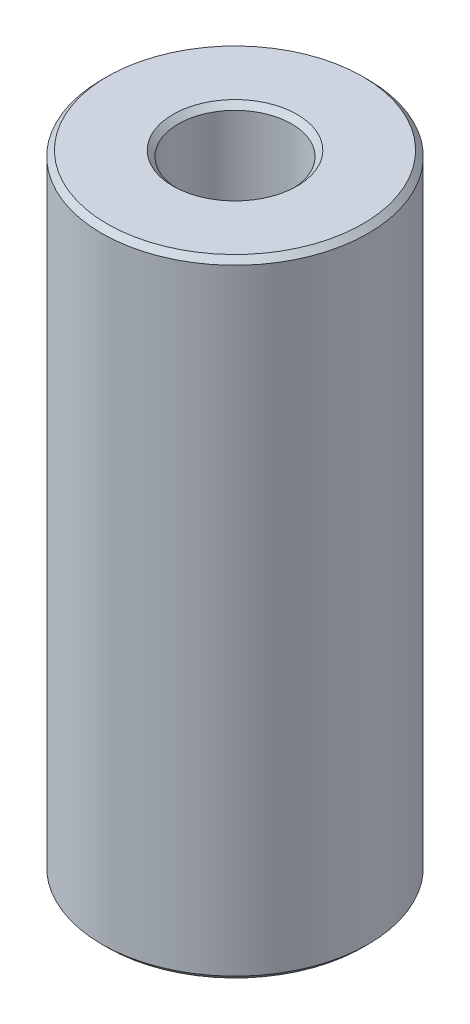
SolidWorks part; units mm, degrees
ref_plane "Front Plane" through (0, 0, 0) normal (0, 0, 1) x (1, 0, 0)
ref_plane "Top Plane" through (0, 0, 0) normal (0, 1, 0) x (1, 0, 0)
ref_plane "Right Plane" through (0, 0, 0) normal (1, 0, 0) x (0, 0, -1)
sketch "Sketch1" plane through (0, 0, 0) normal (0, 1, 0) x (1, 0, 0)
  circle A0 centre (0, 0) radius 47.5
  dimension "SLEEVE_OD" = 95
extrude "Boss-Extrude1" add sketch "Sketch1" along normal blind 223.4758
sketch "Sketch2" plane through (0, 0, 0) normal (0, 1, 0) x (1, 0, 0)
  circle A0 centre (0, 0) radius 20.2059
  dimension "BORE_D" = 40.4119
extrude "Cut-Extrude1" cut sketch "Sketch2" along normal through all
chamfer "Chamfer1" distance 1.9514 angle 45 4 edges at (0, 223.4758, 20.2059) (0, 0, 20.2059) (0, 0, 47.5) (0, 223.4758, 47.5)
